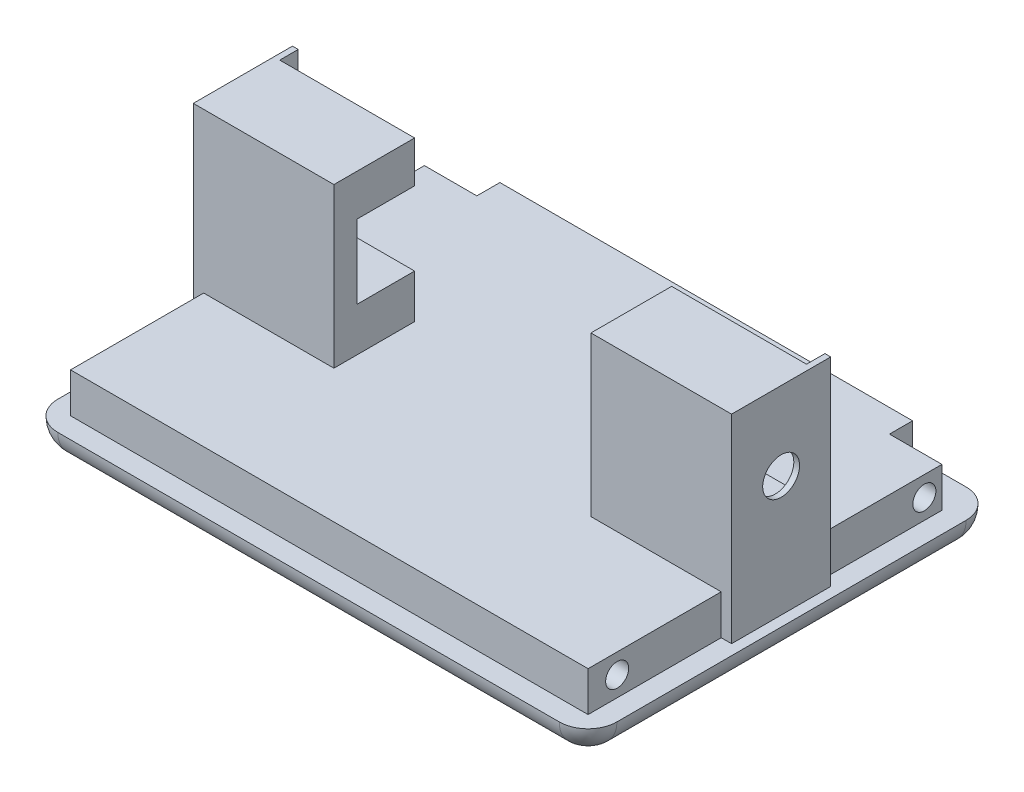
SolidWorks part; units mm, degrees
ref_plane "Front Plane" through (0, 0, 0) normal (0, 0, 1) x (1, 0, 0)
ref_plane "Top Plane" through (0, 0, 0) normal (0, 1, 0) x (1, 0, 0)
ref_plane "Right Plane" through (0, 0, 0) normal (1, 0, 0) x (0, 0, -1)
sketch "Sketch1" plane through (0, 0, 0) normal (0, 1, 0) x (1, 0, 0)
  line L0 (45.3, 0) -> (45.3, 4) construction
  line L1 (0, 0) -> (90.6, 0) construction
  line L2 (0, 0) -> (0, -62.2) construction
  line L3 (0, -62.2) -> (90.6, -62.2) construction
  line L4 (90.6, 0) -> (90.6, -62.2) construction
  line L5 (81.5, 4) -> (9.1, 4) construction
  line L6 (9.1, 4) -> (9.1, 0) construction
  line L7 (81.5, 4) -> (81.5, 0) construction
  line L8 (81.5, 3.6) -> (9.5, 3.6)
  line L9 (9.5, 3.6) -> (9.5, 0)
  line L10 (0.4, -0.4) -> (0.4, -61.8)
  line L11 (0.4, -61.8) -> (90.2, -61.8)
  line L12 (90.2, -0.4) -> (90.2, -61.8)
  line L13 (0.4, -0.4) -> (90.2, -0.4)
  line L14 (81.1, 4) -> (81.1, 0)
  line L15 (9.5, 0) -> (9.5, -0.4)
  line L16 (81.1, 0) -> (81.1, -0.4)
  dimension "D1" = 90.6
  dimension "D2" = 62.2
  dimension "D3" = 36.2
  dimension "D4" = 4
  dimension "D5" = 0.4
  dimension "D6" = 0.4
extrude "Boss-Extrude1" add sketch "Sketch1" along normal blind 6.9 contours L13 L10 L11 L12 | L16 L14 L8 L9 L15 L13 region at (45.3, 0, -1.6) region at (45.3, 0, 31.1)
sketch "Sketch2" plane through (90.2, 0, 0) normal (1, 0, 0) x (0, 0, -1)
  line L0 (-0.4, 0) -> (-61.8, 0) construction
  line L1 (-0.4, 6.9) -> (-6.5, 6.9) construction
  line L2 (-0.4, 6.9) -> (-0.4, 0) construction
  line L3 (-0.4, 0) -> (-6.5, 0) construction
  line L4 (-6.5, 6.9) -> (-6.5, 0) construction
  line L5 (-0.4, 0) -> (0, 0) construction
  line L6 (-3.45, 6.9) -> (-3.45, 0) construction
  circle A0 centre (-3.45, 3.45) radius 2
  dimension "D2" = 4
  dimension "D1" = 3.05
extrude "Cut-Extrude1" cut sketch "Sketch2" against normal blind 4
ref_plane "Plane1" through (45.3, 0, 0) normal (1, 0, 0) x (0, 0, -1)
mirror "Mirror1" about plane through (45.3, 0, 0) normal (1, 0, 0) of "Cut-Extrude1"
ref_plane "Plane2" through (0, 0, 31.1) normal (0, 0, 1) x (1, 0, 0)
sketch "Sketch3" plane through (0, 0, 0) normal (0, 1, 0) x (1, 0, 0)
  line L0 (90.2, -31.1) -> (45.3, -31.1) construction
  line L11 (90.2, -0.4) -> (90.2, -61.8) construction
  line L13 (45.3, 3.6) -> (45.3, -61.8) construction
  line L14 (81.1, 3.6) -> (9.5, 3.6) construction
  line L15 (0.4, -61.8) -> (90.2, -61.8) construction
  line L17 (-3.2, -65.4) -> (93.8, -65.4)
  line L18 (-3.2, -65.4) -> (-3.2, 5.2)
  line L19 (-3.2, 5.2) -> (93.8, 5.2)
  line L20 (93.8, -65.4) -> (93.8, 5.2)
  line L21 (-3.2, -65.4) -> (93.8, 5.2) construction
  line L22 (-3.2, 5.2) -> (93.8, -65.4) construction
  point P11 (45.3, -30.1)
  dimension "D1" = 1
  dimension "D3" = 97
  dimension "D4" = 70.6
extrude "Boss-Extrude2" add sketch "Sketch3" against normal blind 5
sketch "Sketch5" plane through (0.4, 0, 0) normal (-1, 0, 0) x (0, 0, 1)
  line L0 (-5.2, 0) -> (65.4, 0) construction
  line L1 (30.1, 0) -> (30.1, 6.9) construction
  line L2 (38.7, 0) -> (35.3, 0)
  line L3 (0.4, 6.9) -> (61.8, 6.9) construction
  line L4 (24.9, 6.9) -> (24.9, 34.5)
  line L7 (0.4, 0) -> (61.8, 0) construction
  line L12 (35.3, 6.9) -> (35.3, 34.5)
  line L13 (38.7, 34.5) -> (38.7, 0)
  line L14 (35.3, 34.5) -> (38.7, 34.5)
  line L15 (24.9, 0) -> (24.9, 6.9)
  line L16 (35.3, 0) -> (35.3, 6.9)
  line L17 (24.9, 34.5) -> (21.5, 34.5)
  line L18 (21.5, 34.5) -> (21.5, 0)
  line L19 (21.5, 0) -> (24.9, 0)
  line L21 (24.9, 34.5) -> (35.3, 34.5)
  line L22 (24.9, 0) -> (35.3, 0)
  point P30 (30.1, 0)
  line M8 (0.4, 0) -> (61.8, 0)
  line M10 (61.8, 6.9) -> (0.4, 6.9)
  dimension "D1" = 5.2
  dimension "D2" = 3.4
  dimension "D3" = 27.6
extrude "Boss-Extrude3" add sketch "Sketch5" along normal blind 1.8 contours L16 L15 M8 M10 | L18 L15 M10 M8 | L16 L13 M8 M10 region at (0.4, 3.45, 37) region at (0.4, 3.45, 30.1) region at (0.4, 3.45, 23.2)
extrude "Boss-Extrude4" add sketch "Sketch5<3>" against normal blind 1 from surface contours L16 L15 M8 M10 | L21 L4 L12 M10 | L17 L18 L4 M10 | L18 L15 M10 M8 | L16 L13 M8 M10 | L14 L12 L13 M10 region at (0.4, 3.45, 37) region at (0.4, 3.45, 30.1) region at (0.4, 20.7, 37) region at (0.4, 20.7, 30.1) region at (0.4, 3.45, 23.2) region at (0.4, 20.7, 23.2) starting at face at (-1.4, 3.45, 30.1)
sketch "Sketch5<3>" plane through (0.4, 0, 0) normal (-1, 0, 0) x (0, 0, 1) same geometry as "Sketch5"
extrude "Boss-Extrude6" add sketch "Sketch5<5>" against normal blind 1.8 from surface contours L18 L15 M10 M8 | L16 L13 M8 M10 | L16 L15 M8 M10 region at (0.4, 3.45, 37) region at (0.4, 3.45, 30.1) region at (0.4, 3.45, 23.2) starting at face at (90.2, 3.45, 1.45)
sketch "Sketch5<5>" plane through (0.4, 0, 0) normal (-1, 0, 0) x (0, 0, 1) same geometry as "Sketch5"
extrude "Boss-Extrude7" add sketch "Sketch5<7>" along normal blind 1 from surface contours L16 L13 M8 M10 | L14 L12 L13 M10 | L21 L4 L12 M10 | L17 L18 L4 M10 | L18 L15 M10 M8 | L16 L15 M8 M10 region at (0.4, 3.45, 37) region at (0.4, 3.45, 30.1) region at (0.4, 20.7, 37) region at (0.4, 20.7, 30.1) region at (0.4, 3.45, 23.2) region at (0.4, 20.7, 23.2) starting at face at (92, 3.45, 30.1)
sketch "Sketch5<7>" plane through (0.4, 0, 0) normal (-1, 0, 0) x (0, 0, 1) same geometry as "Sketch5"
sketch "Sketch6" plane through (-0.4, 0, 0) normal (1, 0, 0) x (0, 0, -1)
  line L3 (-30.1, 20.9) -> (-30.1, 6.9) construction
  line L4 (-21.5, 6.9) -> (-38.7, 6.9) construction
  circle A0 centre (-30.1, 20.9) radius 3.2
  dimension "D1" = 6.4
  dimension "D2" = 14
extrude "Cut-Extrude2" cut sketch "Sketch6" against normal through all both and the other way through all
sketch "Sketch7" plane through (92, 0, 0) normal (1, 0, 0) x (0, 0, -1)
  line L0 (-30.1, 20.9) -> (-38.7, 20.9) construction
  line L1 (-21.5, 20.9) -> (-30.1, 20.9) construction
  line L2 (-38.7, 20.9) -> (-38.7, 27.3)
  line L3 (-38.7, 20.9) -> (-38.7, 14.5)
  line L4 (-34.7, 14.5) -> (-24.7, 14.5)
  line L5 (-24.7, 14.5) -> (-24.7, 6.9)
  line L6 (-24.7, 6.9) -> (-34.7, 6.9)
  line L7 (-34.7, 34.5) -> (-24.7, 34.5)
  line L8 (-30.1, 20.9) -> (-30.1, 34.5) construction
  line L9 (-38.7, 34.5) -> (-21.5, 34.5) construction
  line L10 (-24.7, 27.3) -> (-24.7, 34.5)
  line L11 (-38.7, 27.3) -> (-34.7, 27.3)
  line L12 (-34.7, 27.3) -> (-34.7, 34.5)
  line L13 (-34.7, 34.5) -> (-38.7, 34.5)
  line L14 (-34.7, 27.3) -> (-24.7, 27.3)
  line L15 (-21.5, 0) -> (-21.5, 34.5) construction
  line L18 (-38.7, 34.5) -> (-38.7, 27.3)
  line L19 (-38.7, 6.9) -> (-38.7, 14.5)
  line L20 (-34.7, 6.9) -> (-38.7, 6.9)
  line L21 (-34.7, 14.5) -> (-34.7, 6.9)
  line L22 (-38.7, 14.5) -> (-38.7, 27.3)
  line L23 (-34.7, 14.5) -> (-34.7, 27.3)
  line L24 (-38.7, 14.5) -> (-34.7, 14.5)
  line M8 (-21.5, 34.5) -> (-38.7, 34.5)
  line M9 (-38.7, 34.5) -> (-38.7, 0)
  dimension "D1" = 6.4
  dimension "D2" = 4
  dimension "D3" = 10
extrude "Boss-Extrude9" add sketch "Sketch7" against normal blind 23.4 from surface contours L24 L20 L21 M9 | L24 L23 L11 M9 | L11 L12 M8 M9 | L21 | L12 region at (92, 20.9, 36.7) region at (92, 30.9, 36.7) region at (92, 10.7, 36.7) region at (92, 30.9, 29.7) region at (92, 10.7, 29.7) starting at face at (91, 20.9, 33.3)
extrude "Boss-Extrude10" add sketch "Sketch7<4>" along normal blind 23.4 from surface contours L4 L21 L6 L5 | L24 L20 L21 M9 | L11 L12 M8 M9 | L12 L14 L10 M8 | L24 L23 L11 M9 region at (92, 20.9, 36.7) region at (92, 30.9, 36.7) region at (92, 10.7, 36.7) region at (92, 30.9, 29.7) region at (92, 10.7, 29.7) starting at face at (-0.4, 20.9, 33.3)
sketch "Sketch7<4>" plane through (92, 0, 0) normal (1, 0, 0) x (0, 0, -1) same geometry as "Sketch7"
sketch "Sketch9" plane through (0, 0, 24.7) normal (0, 0, -1) x (-1, 0, 0)
  line L0 (-91, 34.5) -> (-91, 27.3) construction
  line L3 (-79.3, 34.5) -> (-79.3, 27.3) construction
  line L4 (-67.6, 27.3) -> (-91, 27.3) construction
  line L5 (-79.3, 30.9) -> (-91, 30.9) construction
  circle A0 centre (-85.15, 30.9) radius 2
  circle A1 centre (-73.45, 30.9) radius 2
  dimension "D1" = 4
extrude "Cut-Extrude3" cut sketch "Sketch9" against normal blind 4
mirror "Mirror3" about plane through (45.3, 0, 0) normal (1, 0, 0) of "Cut-Extrude3"
ref_plane "Plane3" through (0, 20.7, 0) normal (0, 1, 0) x (1, 0, 0)
mirror "Mirror4" about plane through (0, 20.7, 0) normal (0, 1, 0) of "Mirror3", "Cut-Extrude3"
fillet "Fillet1" radius 5 4 edges at (-3.2, -2.5, 65.4) (93.8, -2.5, 65.4) (93.8, -2.5, -5.2) (-3.2, -2.5, -5.2)
fillet "Fillet2" radius 5 8 edges at (92.3355, -5, 63.9355) (93.8, -5, 30.1) (92.3355, -5, -3.7355) (45.3, -5, -5.2) (-1.7355, -5, -3.7355) (-3.2, -5, 30.1) (-1.7355, -5, 63.9355) (45.3, -5, 65.4)
sketch "Sketch12" plane through (90.2, 0, 0) normal (1, 0, 0) x (0, 0, -1)
  line L0 (-60.4, 0) -> (0.2, 0) construction
  line L1 (-61.8, 6.9) -> (-51.7, 6.9) construction
  line L2 (-61.8, 6.9) -> (-61.8, 0) construction
  line L3 (-61.8, 0) -> (-51.7, 0) construction
  line L4 (-51.7, 6.9) -> (-51.7, 0) construction
  line L5 (-56.75, 6.9) -> (-56.75, 0) construction
  circle A0 centre (-56.75, 3.45) radius 2
  dimension "D2" = 4
  dimension "D1" = 5.05
extrude "Cut-Extrude6" cut sketch "Sketch12" against normal blind 4
mirror "Mirror5" about plane through (45.3, 0, 0) normal (1, 0, 0) of "Cut-Extrude6"
sketch "Sketch10" plane through (0, 6.9, 0) normal (0, 1, 0) x (1, 0, 0)
  line L0 (-3.2, 0.2) -> (-3.2, -60.4) construction
  line L1 (-3.2, -21.5) -> (93.8, -21.5)
  line L2 (-3.2, -21.5) -> (-3.2, 5.2)
  line L3 (-3.2, 5.2) -> (93.8, 5.2)
  line L4 (93.8, -21.5) -> (93.8, 5.2)
  line L6 (-1.4, -21.5) -> (0.4, -21.5) construction
  line L8 (93.8, -60.4) -> (93.8, 0.2) construction
  line L9 (88.8, 5.2) -> (1.8, 5.2) construction
extrude "Cut-Extrude4" [suppressed] cut sketch "Sketch10" against normal through all both and the other way through all
sketch "Sketch11" plane through (0, 6.9, 0) normal (0, 1, 0) x (1, 0, 0)
  line L0 (-3.2, 0.2) -> (-3.2, -60.4) construction
  line L1 (-3.2, -38.7) -> (93.8, -38.7)
  line L2 (-3.2, -38.7) -> (-3.2, -65.4)
  line L3 (-3.2, -65.4) -> (93.8, -65.4)
  line L4 (93.8, -38.7) -> (93.8, -65.4)
  line L5 (93.8, -60.4) -> (93.8, 0.2) construction
  line L6 (67.6, -38.7) -> (92, -38.7) construction
  line L7 (1.8, -65.4) -> (88.8, -65.4) construction
extrude "Cut-Extrude5" [suppressed] cut sketch "Sketch11" against normal through all both
sketch "Sketch13" plane through (0, 0, 21.5) normal (0, 0, -1) x (-1, 0, 0)
  line L0 (-88, 34.5) -> (-88, 6.9)
  line L1 (-91, 34.5) -> (0.4, 34.5)
  line L2 (-91, 34.5) -> (-91, 6.9)
  line L3 (-91, 6.9) -> (0.4, 6.9)
  line L4 (0.4, 34.5) -> (0.4, 6.9)
  line L5 (-2.6, 34.5) -> (-2.6, 6.9)
  dimension "D1" = 3
  dimension "D2" = 3
extrude "Cut-Extrude7" [suppressed] cut sketch "Sketch13" against normal through all contours L5 L1 L0 L3
